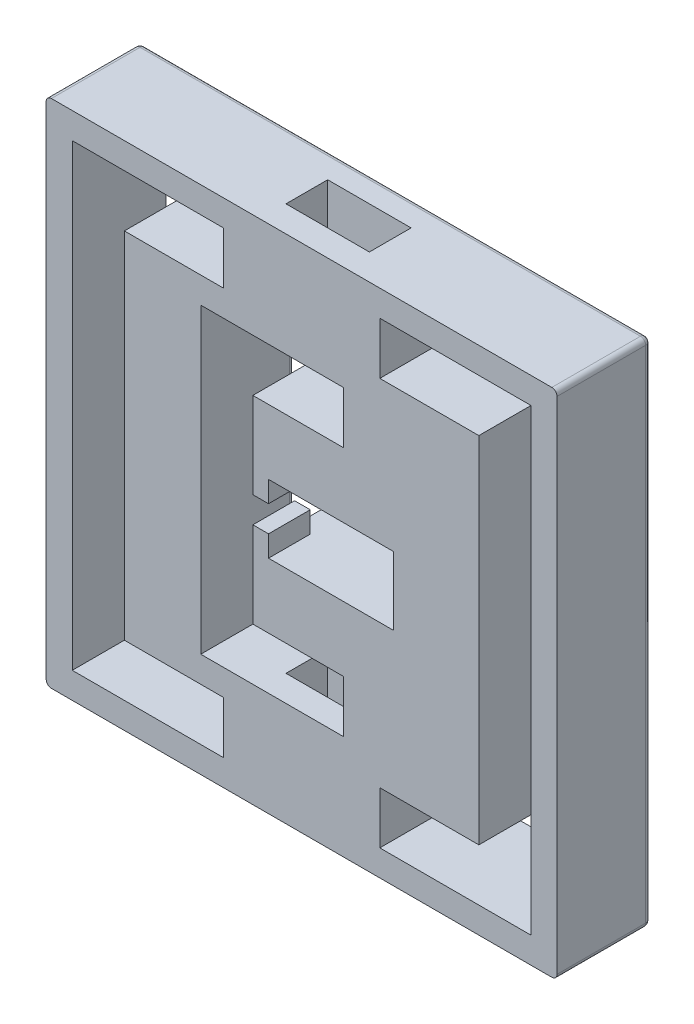
SolidWorks part; units mm, degrees
note: The reader was unsure of these and kept them because the rebuilt part matched: shared geometry of "Sketch2<4>".
ref_plane "Front Plane" through (0, 0, 0) normal (0, 0, 1) x (1, 0, 0)
ref_plane "Top Plane" through (0, 0, 0) normal (0, 1, 0) x (1, 0, 0)
ref_plane "Right Plane" through (0, 0, 0) normal (1, 0, 0) x (0, 0, -1)
sketch "Sketch1" plane through (0, 0, 0) normal (0, 0, 1) x (1, 0, 0)
  line L1 (-49, 49) -> (49, 49)
  line L2 (-49, 49) -> (-49, -49)
  line L3 (-49, -49) -> (49, -49)
  line L4 (49, 49) -> (49, -49)
  line L5 (-49, 49) -> (49, -49) construction
  line L6 (-49, -49) -> (49, 49) construction
  point P0 (0, 0)
  dimension "D1" = 98
  dimension "D2" = 98
extrude "Boss-Extrude1" add sketch "Sketch1" along normal blind 18
sketch "Sketch2" plane through (0, 0, 0) normal (0, 0, -1) x (-1, 0, 0)
  line L0 (0, 6.35) -> (6.35, 6.35)
  line L1 (6.35, 0) -> (6.35, 6.35)
  line L2 (6.35, 6.35) -> (11.55, 6.35)
  line L3 (0, -6.35) -> (6.35, -6.35)
  line L4 (6.35, -6.35) -> (11.55, -6.35)
  line L5 (11.55, -6.35) -> (11.55, 6.35)
  line L6 (6.35, 0) -> (6.35, -6.35)
  line L7 (11.55, -6.35) -> (-22.85, -6.35)
  line L8 (-22.85, -6.35) -> (-22.85, 6.35)
  line L9 (-22.85, 6.35) -> (0, 6.35)
  line L10 (-22.85, 6.35) -> (-17.65, 6.35)
  line L11 (-17.65, 6.35) -> (-17.65, -6.35)
  line L12 (-22.85, 6.55) -> (0, 6.55)
  line L13 (0, 6.55) -> (6.35, 6.55)
  line L14 (6.15, 0) -> (6.15, -6.35)
  line L15 (6.15, 0) -> (6.15, 6.35)
  line L16 (6.35, 6.55) -> (11.75, 6.55)
  line L17 (11.75, -6.35) -> (11.75, 6.55)
  line L18 (0, -6.15) -> (6.35, -6.15)
  line L19 (6.35, -6.15) -> (11.55, -6.15)
  line L20 (11.55, -6.55) -> (-23.05, -6.55)
  line L21 (-23.05, -6.55) -> (-23.05, 6.35)
  line L22 (-22.85, 6.55) -> (-17.45, 6.55)
  line L23 (-17.45, 6.35) -> (-17.45, -6.35)
  line L24 (-22.85, 6.55) -> (-23.05, 6.55)
  line L25 (-23.05, 6.55) -> (-23.05, 6.35)
  line L26 (11.75, -6.35) -> (11.75, -6.55)
  line L27 (11.75, -6.55) -> (11.55, -6.55)
  line L28 (6.35, -6.35) -> (6.35, -6.55)
  line L29 (-17.65, -6.35) -> (-17.65, -6.55)
  line L30 (-17.45, 6.55) -> (-17.45, -6.35) construction
  line L31 (-17.65, 6.35) -> (-17.65, 6.55)
  line L32 (6.35, 6.55) -> (-17.65, 6.55)
  line L33 (-17.65, 6.35) -> (-17.65, 6.55)
  line L34 (-17.65, 6.35) -> (6.35, 6.35)
  line L35 (6.35, 6.55) -> (6.35, 6.35)
  circle A0 centre (0, 0) radius 2.5
  circle A1 centre (0, 0) radius 6.35
  circle A2 centre (0, 0) radius 2.3
  circle A3 centre (0, 0) radius 6.15
  dimension "D1" = 5
  dimension "D2" = 12.7
  dimension "D3" = 5.2
  dimension "D4" = 24
  dimension "D5" = 5.2
  dimension "D6" = 0.2
extrude "Cut-Extrude1" cut sketch "Sketch2" against normal blind 18 contours A1 L9 L11 L7 | A1 A0 | A0 | A1 L1 L0 | A1 L3 L6 | A3 L15 A1 L18 | A2 | A1 L15 L0 | A3 L18 A1 L14 | A1 L14 L18 L6 | A1 L15 L14 | L18 L14 L7 L6 | A1 L3 L14 L18 | L30 L22 L31 L9 | L23 L9 L11 L7 | L7 L29 L20 L28 L3 | L12 L30 L9 L0 L35 L13
extrude "Cut-Extrude2" cut sketch "Sketch2<4>" against normal blind 10 contours L11 L9 L8 L7 | L9 L31 L12 L24 L25 L21 L20 L29 L7 L8 | L6 L19 L5 L2 L1 | L16 L35 L2 L5 L4 L28 L20 L27 L26 L17 | L19 L6 L4 L5
sketch "Sketch2<4>" plane through (0, 0, 0) normal (0, 0, -1) x (-1, 0, 0) same geometry as "Sketch2"
sketch "Sketch4" plane through (0, 0, 10) normal (0, 0, -1) x (-1, 0, 0)
  line L0 (6.35, 0) -> (6.35, 2.5)
  line L1 (6.35, 0) -> (6.35, 6.35) construction
  line L2 (6.35, 0) -> (6.35, -2.5)
  line L3 (6.35, 0) -> (6.35, -6.35) construction
  line L4 (6.35, 2.5) -> (9.35, 2.5)
  line L5 (9.35, 2.5) -> (9.35, -2.5)
  line L6 (9.35, -2.5) -> (6.35, -2.5)
extrude "Cut-Extrude3" cut sketch "Sketch4" against normal blind 8
sketch "Sketch5" plane through (0, 0, 18) normal (0, 0, 1) x (1, 0, 0)
  line L0 (-9.35, 2.5) -> (-19.35, 2.5)
  line L1 (-19.35, 2.5) -> (-19.35, -29)
  line L2 (-49, -49) -> (49, -49) construction
  line L3 (0, -49) -> (8, -49)
  line L4 (0, -49) -> (-8, -49)
  line L5 (8, -49) -> (8, -29)
  line L6 (-8, -49) -> (-8, -29)
  line L7 (-8, -29) -> (-19.35, -29)
  line L8 (8, -29) -> (8, -19)
  line L9 (8, -19) -> (-9.35, -19)
  line L10 (-9.35, -19) -> (-9.35, -2.5)
  line L11 (8, -49) -> (-8, -49)
  line L12 (-9.35, -2.5) -> (-9.35, 2.5)
  line L13 (0, 0) -> (14.3841, 0)
  line L14 (8, 49) -> (-8, 49)
  line L15 (8, 19) -> (-9.35, 19)
  line L16 (8, 29) -> (8, 19)
  line L17 (-8, 49) -> (-8, 29)
  line L18 (8, 49) -> (8, 29)
  line L19 (0, 49) -> (-8, 49)
  line L20 (0, 49) -> (8, 49)
  line L21 (-9.35, 19) -> (-9.35, 2.5)
  line L22 (-8, 29) -> (-19.35, 29)
  line L23 (-19.35, -2.5) -> (-19.35, 29)
  line L24 (-9.35, -2.5) -> (-19.35, -2.5)
  line M18 (-9.35, -2.5) -> (-9.35, 2.5)
  line M20 (49, 49) -> (-49, 49)
  line M22 (-49, -49) -> (49, -49)
extrude "Cut-Extrude4" cut sketch "Sketch5" against normal blind 18 contours L9 L10 L0 L1 L7 L6 L5 L8 M18 M22 | L23 L0 L21 L15 L16 L18 L14 L17 L22 M20 | L24 L0 L1 M18
sketch "Sketch6" plane through (-8, 0, 0) normal (1, 0, 0) x (0, 0, -1)
  line L0 (-18, 49) -> (-18, 29)
  line L1 (-18, 29) -> (-13, 29)
  line L2 (0, 29) -> (-18, 29) construction
  line L3 (-13, 29) -> (-13, 49)
  line L4 (0, 49) -> (-18, 49) construction
  line L5 (-13, 49) -> (-18, 49)
  line L6 (0, 49) -> (-5, 49)
  line L7 (-5, 49) -> (-5, 29)
  line L8 (-5, 29) -> (0, 29)
  line L9 (0, 29) -> (0, 49)
  line L10 (-18, -29) -> (-18, -49)
  line L11 (-18, -49) -> (-13, -49)
  line L12 (0, -49) -> (-18, -49) construction
  line L13 (-13, -49) -> (-13, -29)
  line L14 (0, -29) -> (-18, -29) construction
  line L15 (-13, -29) -> (-18, -29)
  line L16 (0, -29) -> (0, -49)
  line L17 (0, -49) -> (-5, -49)
  line L18 (-5, -49) -> (-5, -29)
  line L19 (-5, -29) -> (0, -29)
extrude "Boss-Extrude2" add sketch "Sketch6" along normal blind 16
fillet "Fillet1" radius 1 16 edges at (0, 49, 0) (-49, 0, 0) (0, -49, 0) (49, 0, 0) (-19.35, 0, 0) (-5.675, 29, 0) (8, 24, 0) (-0.675, 19, 0) (-9.35, 12.775, 0) (6.85, 6.55, 0) (23.05, 0, 0) (6.85, -6.55, 0) (-9.35, -12.775, 0) (-0.675, -19, 0) (8, -24, 0) (-5.675, -29, 0)
fillet "Fillet2" radius 1 8 edges at (48.7071, 48.7071, 0.2929) (48.7071, -48.7071, 0.2929) (-48.7071, -48.7071, 0.2929) (-48.7071, 48.7071, 0.2929) (49, 49, 9.5) (49, -49, 9.5) (-49, -49, 9.5) (-49, 49, 9.5)
sketch "Sketch8" plane through (0, 0, 18) normal (0, 0, 1) x (1, 0, 0)
  line L0 (-34, -34) -> (-34, 34)
  line L1 (-49, -49) -> (49, -49)
  line L2 (-49, -49) -> (-49, 49)
  line L3 (-49, 49) -> (49, 49)
  line L4 (49, -49) -> (49, 49)
  line L5 (-49, -49) -> (49, 49) construction
  line L6 (-49, 49) -> (49, -49) construction
  line L7 (-34, 34) -> (34, 34)
  line L8 (34, -34) -> (34, 34)
  line L9 (-34, -34) -> (34, -34)
  line L10 (-44, -44) -> (-44, 44)
  line L11 (-44, 44) -> (44, 44)
  line L12 (44, -44) -> (44, 44)
  line L13 (-44, -44) -> (44, -44)
  line L14 (0, 34) -> (-15, 34)
  line L15 (0, 34) -> (15, 34)
  line L16 (0, -34) -> (15, -34)
  line L17 (0, -34) -> (-15, -34)
  line L18 (-15, -34) -> (-15, -44)
  line L19 (15, -34) -> (15, -44)
  line L20 (15, 34) -> (15, 44)
  line L21 (-15, 34) -> (-15, 44)
  point P0 (0, 0)
  dimension "D1" = 15
  dimension "D2" = 5
extrude "Cut-Extrude5" cut sketch "Sketch8" against normal blind 18 contours L7 L21 L11 L10 L13 L18 L9 L0 | L20 L7 L8 L9 L19 L13 L12 L11
